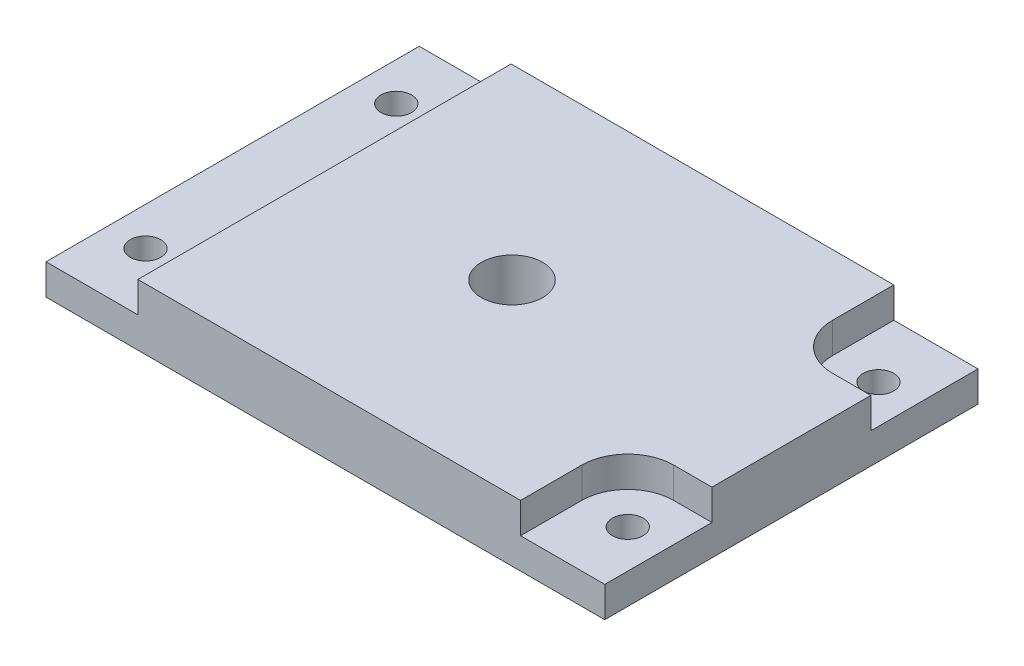
SolidWorks part; units mm, degrees
ref_plane "Front Plane" through (0, 0, 0) normal (0, 0, 1) x (1, 0, 0)
ref_plane "Top Plane" through (0, 0, 0) normal (0, 1, 0) x (1, 0, 0)
ref_plane "Right Plane" through (0, 0, 0) normal (1, 0, 0) x (0, 0, -1)
sketch "Sketch1" plane through (0, 0, 0) normal (0, 1, 0) x (1, 0, 0)
  line L1 (-25, -13) -> (25, -13) construction
  line L2 (-25, -13) -> (-25, 13) construction
  line L3 (-25, 13) -> (25, 13) construction
  line L4 (25, -13) -> (25, 13) construction
  line L5 (-25, -13) -> (25, 13) construction
  line L6 (-25, 13) -> (25, -13) construction
  line L7 (-28.9688, -19.35) -> (28.9688, -19.35)
  line L8 (-28.9688, -19.35) -> (-28.9688, 19.35)
  line L9 (-28.9688, 19.35) -> (28.9688, 19.35)
  line L10 (28.9688, -19.35) -> (28.9688, 19.35)
  line L11 (-28.9688, -19.35) -> (28.9688, 19.35) construction
  line L12 (-28.9688, 19.35) -> (28.9688, -19.35) construction
  circle A0 centre (-25, 13) radius 1.5875
  circle A1 centre (25, 13) radius 1.5875
  circle A2 centre (25, -13) radius 1.5875
  circle A3 centre (-25, -13) radius 1.5875
  circle A4 centre (0, 0) radius 3.175
  point P0 (0, 0)
  point P10 (0, 0)
  dimension "D1" = 50
  dimension "D3" = 3.175
  dimension "D6" = 6.35
  dimension "D2" = 26
  dimension "D4" = 6.35
  dimension "D5" = 3.9688
extrude "Boss-Extrude1" add sketch "Sketch1" along normal blind 6.35
sketch "Sketch2" plane through (0, 6.35, 0) normal (0, 1, 0) x (1, 0, 0)
  line L0 (-28.9688, -19.35) -> (28.9688, -19.35) construction
  line L1 (-28.9688, 19.35) -> (-19.4438, 19.35)
  line L2 (-28.9688, 19.35) -> (-28.9688, -19.35)
  line L3 (-28.9688, -19.35) -> (-19.4438, -19.35)
  line L4 (-19.4438, 19.35) -> (-19.4438, -19.35)
  line L5 (20.2375, -19.35) -> (20.2375, -13)
  line L6 (28.9688, -8.2375) -> (25, -8.2375)
  line L7 (28.9688, -19.35) -> (28.9688, 19.35) construction
  line L8 (28.9688, 8.2375) -> (25, 8.2375)
  line L9 (20.2375, 19.35) -> (20.2375, 13)
  line L10 (28.9688, 19.35) -> (-28.9688, 19.35) construction
  line L11 (20.2375, 19.35) -> (28.9688, 19.35)
  line L12 (28.9688, 19.35) -> (28.9688, 8.2375)
  line L13 (28.9688, -8.2375) -> (28.9688, -19.35)
  line L14 (28.9688, -19.35) -> (20.2375, -19.35)
  arc A0 (20.2375, 13) -> (25, 8.2375) centre (25, 13) ccw
  arc A1 (20.2375, -13) -> (25, -8.2375) centre (25, -13) cw
  dimension "D1" = 4.7625
  dimension "D2" = 9.525
extrude "Cut-Extrude1" cut sketch "Sketch2" against normal blind 3.175
